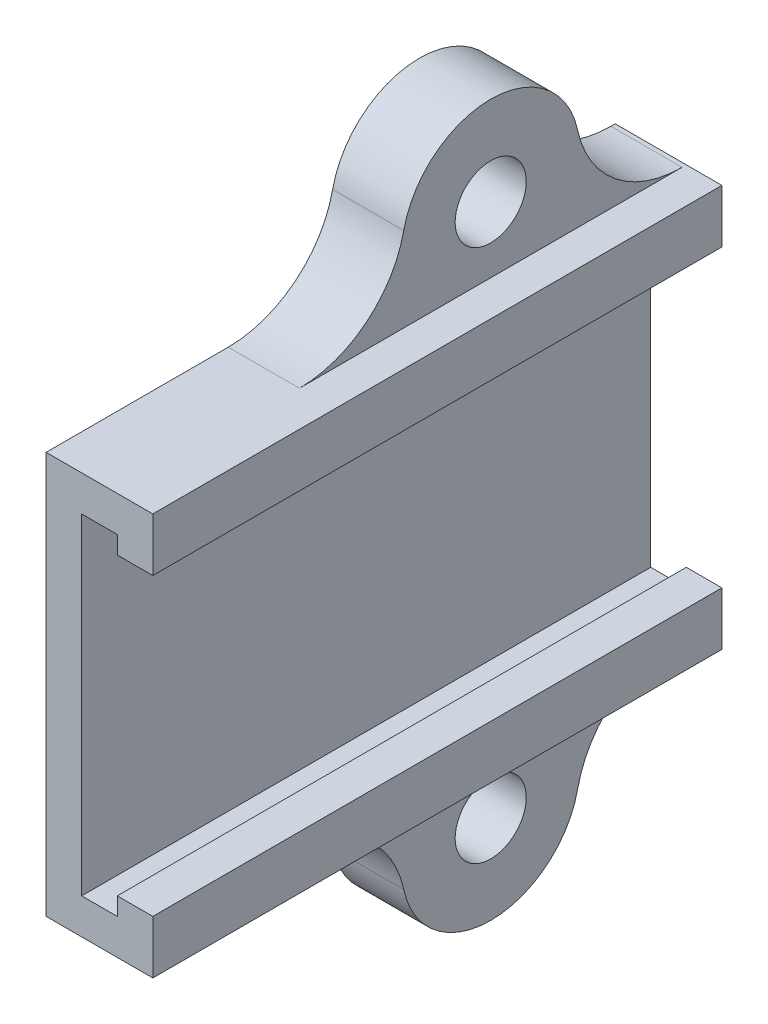
SolidWorks part; units mm, degrees
ref_plane "Plan de face" through (0, 0, 0) normal (0, 0, 1) x (1, 0, 0)
ref_plane "Plan de dessus" through (0, 0, 0) normal (0, 1, 0) x (1, 0, 0)
ref_plane "Plan de droite" through (0, 0, 0) normal (1, 0, 0) x (0, 0, -1)
sketch "Esquisse1" plane through (0, 0, 0) normal (0, 0, 1) x (1, 0, 0)
  line L0 (4, -2) -> (4, 1)
  line L1 (0, 0) -> (2, 0)
  line L2 (0, 0) -> (0, 18.6)
  line L3 (0, 18.6) -> (2, 18.6)
  line L4 (2, 0) -> (2, 18.6) construction
  line L5 (-2, -2) -> (4, -2)
  line L6 (-2, -2) -> (-2, 20.6)
  line L7 (-2, 20.6) -> (4, 20.6)
  line L8 (4, -2) -> (4, 20.6) construction
  line L9 (4, 1) -> (2, 1)
  line L10 (2, 1) -> (2, 0)
  line L11 (2, 18.6) -> (2, 17.6)
  line L12 (2, 17.6) -> (4, 17.6)
  line L13 (4, 17.6) -> (4, 20.6)
  point P9 (1, 20.6)
  dimension "D1" = 2
  dimension "D2" = 18.6
  dimension "D3" = 2
  dimension "D4" = 2
  dimension "D5" = 2
  dimension "D6" = 2
  dimension "D7" = 1
  dimension "D8" = 1
extrude "Boss.-Extru.1" add sketch "Esquisse1" along normal blind 32
sketch "Esquisse2" plane through (-2, 0, 0) normal (-1, 0, 0) x (0, 0, 1)
  line L0 (32, 20.6) -> (0, 20.6) construction
  line L1 (32, -2) -> (0, -2) construction
  line L2 (6, -2) -> (6, -5.7)
  line L3 (6, -5.7) -> (16, -5.7) construction
  line L4 (16, -5.7) -> (16, -2)
  line L6 (6, 20.6) -> (6, 24.3)
  line L7 (6, 24.3) -> (16, 24.3) construction
  line L8 (16, 24.3) -> (16, 20.6)
  line L10 (6, 20.6) -> (16, 20.6)
  line L11 (16, -2) -> (6, -2)
  line L12 (0, 20.6) -> (0, -2) construction
  arc A0 (6, 24.3) -> (16, 24.3) centre (11, 24.3) cw
  arc A1 (6, -5.7) -> (16, -5.7) centre (11, -5.7) ccw
  circle A2 centre (11, -5.7) radius 2
  circle A3 centre (11, 24.3) radius 2
  point P14 (11, -5.7)
  point P20 (11, 24.3)
  point P27 (6, -3.85)
  dimension "D4" = 4
  dimension "D1" = 30
  dimension "D5" = 6
  dimension "D6" = 10
extrude "Boss.-Extru.2" add sketch "Esquisse2" against normal blind 4
fillet "Congé1" radius 6 4 edges at (0, -2, 16) (0, 20.6, 16) (0, -2, 6) (0, 20.6, 6)
sketch "Esquisse3" plane through (0, 0, 0) normal (1, 0, 0) x (0, 0, -1)
  line L1 (0, 18.6) -> (-8, 18.6)
  line L2 (0, 18.6) -> (0, 10.6)
  line L3 (0, 10.6) -> (-8, 10.6)
  line L4 (-8, 18.6) -> (-8, 10.6)
  dimension "D1" = 8
  dimension "D2" = 8
